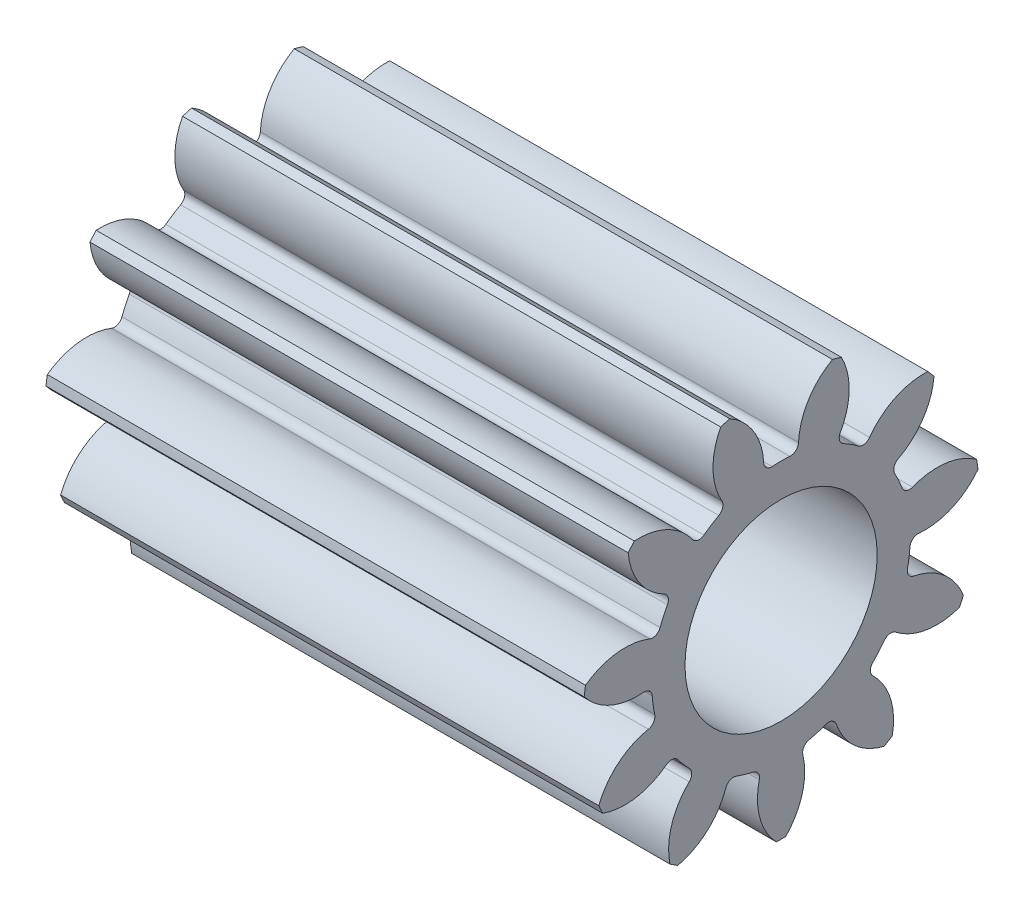
SolidWorks part; units mm, degrees
ref_plane "Plane1" through (0, 0, 0) normal (0, 0, 1) x (1, 0, 0)
ref_plane "Plane2" through (0, 0, 0) normal (0, 1, 0) x (1, 0, 0)
ref_plane "Plane3" through (0, 0, 0) normal (1, 0, 0) x (0, 0, -1)
other "Configuration Table"
sketch "HoldingSke" plane through (0, 0, 0) normal (0, 1, 0) x (1, 0, 0)
  line L0 (0, 0) -> (797.8666, -155.0896)
  line L1 (-15, 0) -> (100, 0) construction
  line L2 (0, 0) -> (-2.1039, 2.3779)
  line L3 (0, 0) -> (-11.863, 4.5341)
  line L4 (0, 0) -> (8.4773, 1.6478)
  line L5 (0, 0) -> (-47.5972, -17.7524)
  line L6 (0, 0) -> (-10.5278, -7.1032)
  line L7 (-2.1039, 2.3779) -> (8.8309, 51.9876)
  line L8 (-76.2, 54.61) -> (-75.184, 54.61)
  line L9 (-71.009, 38.7566) -> (-53.1078, 45.2721)
  line L10 (-76.2, 71.12) -> (104.1128, 71.12)
  line L11 (0, 0) -> (-12.7, 0)
  line L12 (-76.2, 101.6) -> (-76.1716, 101.6)
  line L13 (24.9733, 27.94) -> (52.9518, 28.4284)
  line L14 (24.9733, 27.94) -> (25.0241, 27.9398)
  line L15 (24.9733, 27.94) -> (100.4021, 29.52)
  circle A0 centre (0, 0) radius 0.3969
  circle A1 centre (0, 0) radius 3.3623
  circle A2 centre (0, 0) radius 38.1
  circle A3 centre (0, 0) radius 0.3969
  dimension "MHD" = 6.7246
  dimension "Hub_dia" = 76.2
  dimension "Bore" = 0.7937
  dimension "MBD" = 0.7937
  dimension "Num_teeth" = 11
  dimension "Pitch" = 812.8
  dimension "Overall_len" = 50.8
  dimension "Show_teeth" = 11
  dimension "Thickness" = 12.7
  dimension "OAL" = 50.8005
  dimension "T_dim" = 1.016
  dimension "Ap" = 20
  dimension "H" = 19.05
  dimension "Pitch_radius" = 180.3128
  dimension "Width" = 12.7
  dimension "Backlash" = 0.0284
  dimension "Addendum_fac" = 1
  dimension "Dedendum_fac" = 1.2
  dimension "Clearance_fac" = 0.2
  dimension "Dedendum_add" = 0.0508
sketch "BasProSke" plane through (0, 0, 0) normal (0, 1, 0) x (1, 0, 0)
  line L0 (-10, 0) -> (60, 0) construction
  line L1 (0, 0) -> (0, 5.1594)
  line L2 (0, 0) -> (14, 0)
  line L3 (14, 0) -> (14, 5.1594)
  line L4 (14, 5.1594) -> (0, 5.1594)
  dimension "Thickness" = 14
  dimension "Diameter" = 10.3187
revolve "Base-Revolve" add sketch "BasProSke" angle 360 about L0
sketch "TooCutSke" plane through (0, 0, 0) normal (1, 0, 0) x (0, 0, -1)
  line L1 (0, 0) -> (0, 107) construction
  line L2 (0, 0) -> (-0.671, 4.3138) construction
  line L3 (0, 0) -> (-2.4387, 8.3055) construction
  line L4 (-0.671, 4.3138) -> (-1.2194, 4.1527) construction
  arc A0 (0.4557, 3.3313) -> (-0.4557, 3.3313) centre (0, 0) ccw
  arc A1 (1.3674, 5.0012) -> (-1.3674, 5.0012) centre (0, 0) ccw
  circle A2 centre (0, 0) radius 4.3656 construction
  circle A3 centre (0, 0) radius 4.1023 construction
  arc A4 (-0.4557, 3.3313) -> (-1.3674, 5.0012) centre (-2.1969, 3.4645) ccw
  arc A5 (1.3674, 5.0012) -> (0.4557, 3.3313) centre (2.1969, 3.4645) ccw
  dimension "Root_dia" = 6.7246
  dimension "Overcut_dia" = 10.3696
  dimension "Pitch_dia" = 8.7312
  dimension "Base_dia" = 8.2047
  dimension "Flank_rad" = 1.7463
  dimension "Half_ang" = 16.364
  dimension "Half_CT" = 0.5715
extrude "ToothCut" cut sketch "TooCutSke" along normal through all
fillet "Breaks" [suppressed] radius 0.0159 tangent propagation no
fillet "RootFillets" radius 0.2095 2 edges at (7, 3.3313, -0.4557) (7, 3.3313, 0.4557)
pattern_circular "TeethCuts" count 11 every 32.727 about axis through (-10, 0, 0) along (1, 0, 0) of "ToothCut", "RootFillets", "Breaks"
sketch "HubNeaOneSke" plane through (0, 0, 0) normal (-1, 0, 0) x (0, 0, 1)
  circle A0 centre (0, 0) radius 3.3623
  dimension "Diameter" = 6.7246
extrude "HubNearOne" [suppressed] add sketch "HubNeaOneSke" along normal blind 36.8005
sketch "HubNeaBotSke" plane through (0, 0, 0) normal (-1, 0, 0) x (0, 0, 1)
  circle A0 centre (0, 0) radius 3.3623
  dimension "Diameter" = 6.7246
extrude "HubNearBoth" [suppressed] add sketch "HubNeaBotSke" along normal blind 18.4003
ref_plane "FarPln" through (14, 0, 0) normal (1, 0, 0) x (0, 0, -1)
sketch "HubFarSke" plane through (14, 0, 0) normal (1, 0, 0) x (0, 0, -1)
  circle A0 centre (0, 0) radius 3.3623
  dimension "Diameter" = 6.7246
extrude "HubFar" [suppressed] add sketch "HubFarSke" along normal blind 18.4003
sketch "BorSke" plane through (0, 0, 0) normal (1, 0, 0) x (0, 0, -1)
  circle A0 centre (0, 0) radius 0.3969
  dimension "Diameter" = 0.7937
extrude "Bore" [suppressed] cut sketch "BorSke" along normal mid plane 101.601
sketch "KeySke" plane through (0, 0, 0) normal (1, 0, 0) x (0, 0, -1)
  line L0 (-0.127, 0) -> (-0.127, 0.6191)
  line L1 (-0.127, 0.6191) -> (0.127, 0.6191)
  line L2 (0.127, 0.6191) -> (0.127, 0)
  line L3 (0, 0) -> (0, 34) construction
  line L4 (-0.127, 0) -> (0.127, 0)
  dimension "Offset" = 0.6191
  dimension "Width" = 0.254
extrude "Keyway" [suppressed] cut sketch "KeySke" along normal mid plane 101.601
pattern_circular "Keyway2" [suppressed] count 2 every 90 about axis through (-10, 0, 0) along (1, 0, 0) reverse direction yes
sketch "Sketch1" plane through (14, 0, 0) normal (1, 0, 0) x (0, 0, -1)
  circle A0 centre (0, 0) radius 2.5
  dimension "D1" = 5
extrude "Cut-Extrude1" cut sketch "Sketch1" against normal up to next
equation "' \"Pitch@HoldingSke\" = 4"
equation "' \"Num_teeth@HoldingSke\" = 12"
equation "' \"Ap@HoldingSke\" =  20"
equation "' \"Ap@HoldingSke\" = 20"
equation "' \"Width@HoldingSke\" = 0.5"
equation "' \"Hub_dia@HoldingSke\"= 1"
equation "' \"Hub_dia@HoldingSke\" = 1"
equation "' \"Overall_len@HoldingSke\" = 1.0"
equation "' \"Bore@HoldingSke\" = 0.75"
equation "' \"T_dim@HoldingSke\" = 0.85"
equation "' \"Width@KeySke\" = 0.25"
equation "' \"Show_teeth@HoldingSke\" = 13"
equation "' \"Backlash@HoldingSke\" = 0.009"
equation "' \"Addendum_fac@HoldingSke\" = 1.0"
equation "' \"Dedendum_fac@HoldingSke\" = 1.25"
equation "' \"Dedendum_add@HoldingSke\" = 0.00005"
equation "' \"Clearance_fac@HoldingSke\" = 0.25"
equation "' \"Pitch@HoldingSke\" = 0.5"
equation "' \"Num_teeth@HoldingSke\" = 23"
equation "' \"Show_teeth@HoldingSke\" = 23"
equation "' \"Backlash@HoldingSke\" = 0.0375"
equation "\"Overcut_dia@TooCutSke\" = (\"Num_teeth@HoldingSke\" + 2 * \"Addendum_fac@HoldingSke\") / \"Pitch@HoldingSke\" + 0.002"
equation "\"Pitch_dia@TooCutSke\" = \"Num_teeth@HoldingSke\" / \"Pitch@HoldingSke\""
equation "\"Base_dia@TooCutSke\" = \"Num_teeth@HoldingSke\" / \"Pitch@HoldingSke\" * cos((\"Ap@HoldingSke\"  * 3.14159265 / 180))"
equation "\"Root_dia@TooCutSke\" = (\"Num_teeth@HoldingSke\" + 2) / \"Pitch@HoldingSke\" - 2 * (\"Addendum_fac@HoldingSke\" + \"Dedendum_fac@HoldingSke\") / \"Pitch@HoldingSke\" - \"Dedendum_add@HoldingSke\" * 2"
equation "\"Half_ang@TooCutSke\" = 180 / \"Num_teeth@HoldingSke\""
equation "\"Half_CT@TooCutSke\" = \"Num_teeth@HoldingSke\" / \"Pitch@HoldingSke\" * sin((3.14159265 / 2 / \"Num_teeth@HoldingSke\")) / 2 - 7 * \"Backlash@HoldingSke\" / 4"
equation "\"Flank_rad@TooCutSke\" = \"Num_teeth@HoldingSke\" / \"Pitch@HoldingSke\" / 5"
equation "\"Radius@RootFillets\" = \"Clearance_fac@HoldingSke\" / \"Pitch@HoldingSke\" + \"Dedendum_add@HoldingSke\""
equation "\"Break_rad@Breaks\" = 0.02 / \"Pitch@HoldingSke\""
equation "\"Thickness@HoldingSke\" = \"Width@HoldingSke\""
equation "\"OAL@HoldingSke\" = \"Thickness@HoldingSke\""
equation "\"MHD@HoldingSke\" = (\"Num_teeth@HoldingSke\" + 2) / \"Pitch@HoldingSke\" - 2 * (\"Addendum_fac@HoldingSke\" + \"Dedendum_fac@HoldingSke\")  / \"Pitch@HoldingSke\" - \"Dedendum_add@HoldingSke\" * 2"
equation "\"MBD@HoldingSke\" = (\"Num_teeth@HoldingSke\" + 2) / \"Pitch@HoldingSke\" - 2 * (\"Addendum_fac@HoldingSke\" + \"Dedendum_fac@HoldingSke\")  / \"Pitch@HoldingSke\" - \"Dedendum_add@HoldingSke\" * 2 - 0.002"
equation "\"MHD@HoldingSke\" = ((sgn( \"MHD@HoldingSke\" - \"Hub_dia@HoldingSke\" )-1)*( \"MHD@HoldingSke\" - \"Hub_dia@HoldingSke\" ))/-2+ \"Hub_dia@HoldingSke\""
equation "\"MBD@HoldingSke\" = ((sgn( \"MBD@HoldingSke\" - \"Bore@HoldingSke\" )-1)*( \"MBD@HoldingSke\" - \"Bore@HoldingSke\" ))/-2+ \"Bore@HoldingSke\""
equation "\"OAL@HoldingSke\" = ((sgn( \"OAL@HoldingSke\" - \"Overall_len@HoldingSke\" )+1)*( \"OAL@HoldingSke\" - \"Overall_len@HoldingSke\" ))/2 + \"Overall_len@HoldingSke\" + 0.000002"
equation "\"Num_teeth@TeethCuts\" = int( \"Show_teeth@HoldingSke\" ) + 1"
equation "\"Num_teeth@TeethCuts\" = ((sgn( \"Num_teeth@TeethCuts\" - \"Num_teeth@HoldingSke\" )-1)*( \"Num_teeth@TeethCuts\" - \"Num_teeth@HoldingSke\" ))/-2+ \"Num_teeth@HoldingSke\""
equation "\"Num_teeth@TeethCuts\" = ((sgn( \"Num_teeth@TeethCuts\" - 2.0)+1)*( \"Num_teeth@TeethCuts\" - 2.0))/2 +2.0"
equation "\"Angle@TeethCuts\" = 360.0 / \"Num_teeth@HoldingSke\""
equation "\"Diameter@BasProSke\" = (\"Num_teeth@HoldingSke\" + 2 * \"Addendum_fac@HoldingSke\") / \"Pitch@HoldingSke\""
equation "\"Thickness@BasProSke\"=14mm"
equation "' \"Fillet_rad@BasProSke\" =  \"Thickness@HoldingSke\" * 0.05"
equation "' \"Fillet_rad@BasProSke\" = \"Thickness@HoldingSke\" * 0.05"
equation "\"MHD@HoldingSke\" = ((sgn( \"MHD@HoldingSke\" - \"Root_dia@TooCutSke\" )-1)*( \"MHD@HoldingSke\" - \"Root_dia@TooCutSke\" ))/-2+ \"Root_dia@TooCutSke\""
equation "\"Diameter@HubNeaOneSke\" = \"MHD@HoldingSke\""
equation "\"Length@HubNearOne\" = \"OAL@HoldingSke\" - \"Thickness@BasProSke\""
equation "\"Diameter@HubNeaBotSke\" = \"MHD@HoldingSke\""
equation "\"Length@HubNearBoth\" = ( \"OAL@HoldingSke\" - \"Thickness@BasProSke\" ) / 2.0"
equation "\"Thickness@FarPln\" = \"Thickness@BasProSke\""
equation "\"Diameter@HubFarSke\" = \"MHD@HoldingSke\""
equation "\"Length@HubFar\" = ( \"OAL@HoldingSke\" - \"Thickness@BasProSke\" ) / 2.0"
equation "\"Diameter@BorSke\" = \"MBD@HoldingSke\""
equation "\"D1@Bore\" = \"OAL@HoldingSke\" * 2.0"
equation "\"D1@Keyway\" = \"OAL@HoldingSke\" * 2.0"
equation "\"Offset@KeySke\" = \"T_dim@HoldingSke\" - \"MBD@HoldingSke\" / 2.0"
equation "\"D1@Sketch1\"=5mm"
